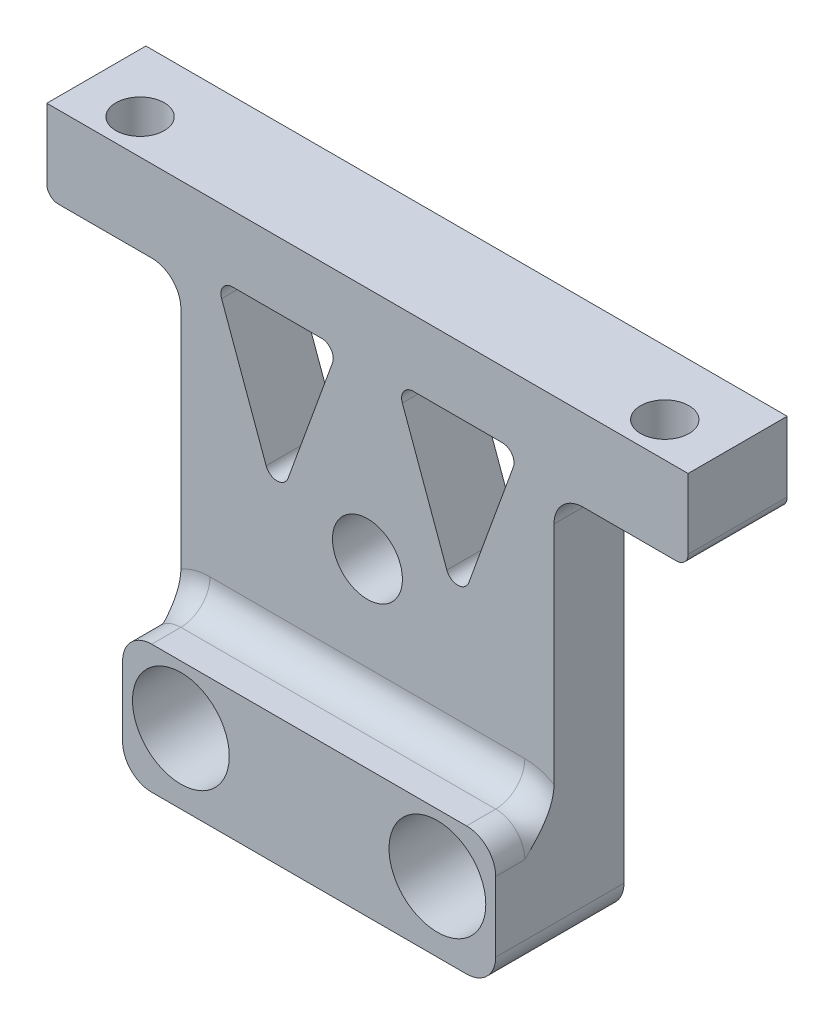
SolidWorks part; units mm, degrees
ref_plane "Front Plane" through (0, 0, 0) normal (0, 0, 1) x (1, 0, 0)
ref_plane "Top Plane" through (0, 0, 0) normal (0, 1, 0) x (1, 0, 0)
ref_plane "Right Plane" through (0, 0, 0) normal (1, 0, 0) x (0, 0, -1)
sketch "Esboço1" plane through (0, 0, 0) normal (0, 0, 1) x (1, 0, 0)
  line L0 (-194.983, 169.5286) -> (-202.6205, 148.5298)
  line L1 (-193, 100.2122) -> (-247, 100.2122)
  line L2 (-188, 105.2122) -> (-188, 164.5682)
  line L4 (-252, 105.2122) -> (-252, 164.5682)
  line L5 (-212.1375, 172.2122) -> (-196.8625, 172.2122)
  line L6 (-220, 183.5682) -> (-220, 100.2122) construction
  line L7 (-275, 183.5682) -> (-165, 183.5682)
  line L8 (-275, 183.5682) -> (-275, 171.5682)
  line L9 (-273, 169.5682) -> (-257, 169.5682)
  line L10 (-165, 183.5682) -> (-165, 171.5682)
  line L11 (-183, 169.5682) -> (-167, 169.5682)
  line L12 (-206.3795, 148.5298) -> (-214.017, 169.5286)
  line L13 (0, 100.2122) -> (-440, 100.2122) construction
  line L15 (-233.6205, 148.5298) -> (-225.983, 169.5286)
  line L16 (-227.8625, 172.2122) -> (-243.1375, 172.2122)
  line L17 (-245.017, 169.5286) -> (-237.3795, 148.5298)
  line L19 (-219, 172.2122) -> (-252, 172.2122) construction
  line L20 (-219, 172.2122) -> (-188, 172.2122) construction
  arc A0 (-202.6205, 148.5298) -> (-206.3795, 148.5298) centre (-204.5, 149.2135) cw
  arc A1 (-194.983, 169.5286) -> (-196.8625, 172.2122) centre (-196.8625, 170.2122) ccw
  arc A2 (-212.1375, 172.2122) -> (-214.017, 169.5286) centre (-212.1375, 170.2122) ccw
  circle A3 centre (-242, 112.2122) radius 8.3
  arc A4 (-225.983, 169.5286) -> (-227.8625, 172.2122) centre (-227.8625, 170.2122) ccw
  arc A5 (-243.1375, 172.2122) -> (-245.017, 169.5286) centre (-243.1375, 170.2122) ccw
  circle A6 centre (-198, 112.2122) radius 8.3
  arc A7 (-233.6205, 148.5298) -> (-237.3795, 148.5298) centre (-235.5, 149.2135) cw
  arc A8 (-167, 169.5682) -> (-165, 171.5682) centre (-167, 171.5682) ccw
  circle A9 centre (-220, 143.3622) radius 6
  arc A10 (-193, 100.2122) -> (-188, 105.2122) centre (-193, 105.2122) ccw
  arc A11 (-247, 100.2122) -> (-252, 105.2122) centre (-247, 105.2122) cw
  arc A12 (-188, 164.5682) -> (-183, 169.5682) centre (-183, 164.5682) cw
  arc A13 (-257, 169.5682) -> (-252, 164.5682) centre (-257, 164.5682) cw
  arc A14 (-275, 171.5682) -> (-273, 169.5682) centre (-273, 171.5682) ccw
  point P17 (-188, 100.2122)
  point P40 (-165, 169.5682)
  point P41 (-204.5, 143.3622)
  point P44 (-194.0069, 172.2122)
  point P47 (-214.9931, 172.2122)
  point P50 (-225.0069, 172.2122)
  point P53 (-245.9931, 172.2122)
  point P56 (-235.5, 143.3622)
  point P59 (-275, 169.5682)
  dimension "D6" = 5
  dimension "D9" = 5
  dimension "D10" = 2
  dimension "D11" = 2
  dimension "D4" = 10
  dimension "D5" = 10
  dimension "D7" = 110
  dimension "D8" = 14
  dimension "D1" = 43.15
  dimension "D2" = 12
  dimension "D3" = 12
extrude "Ressalto-extrusão1" add sketch "Esboço1" along normal blind 12
sketch "Esboço2" plane through (0, 0, 12) normal (0, 0, 1) x (1, 0, 0)
  line L6 (-252, 164.5682) -> (-252, 105.2122) construction
  line L7 (-247, 122.2122) -> (-193, 122.2122)
  line L8 (-252, 117.2122) -> (-252, 105.2122)
  line L9 (-247, 100.2122) -> (-193, 100.2122)
  line L10 (-188, 117.2122) -> (-188, 105.2122)
  line L11 (0, 100.2122) -> (-440, 100.2122) construction
  arc A0 (-193, 100.2122) -> (-188, 105.2122) centre (-193, 105.2122) ccw
  arc A1 (-193, 122.2122) -> (-188, 117.2122) centre (-193, 117.2122) cw
  arc A2 (-252, 105.2122) -> (-247, 100.2122) centre (-247, 105.2122) ccw
  arc A3 (-247, 122.2122) -> (-252, 117.2122) centre (-247, 117.2122) ccw
  circle A6 centre (-242, 112.2122) radius 8.3
  circle A7 centre (-242, 112.2122) radius 8.3
  circle A9 centre (-198, 112.2122) radius 8.3
  circle A10 centre (-198, 112.2122) radius 8.3
  point P10 (-188, 100.2122)
  point P13 (-188, 122.2122)
  point P18 (-252, 122.2122)
  dimension "D2" = 5
  dimension "D1" = 22
  dimension "D3" = 0
  dimension "D4" = 0
extrude "Ressalto-extrusão2" add sketch "Esboço2" along normal blind 10
fillet "Filete1" radius 5 3 edges at (-189.4645, 120.7477, 12) (-250.5355, 120.7477, 12) (-220, 122.2122, 12)
sketch "Esboço3" plane through (0, 169.5682, 0) normal (0, -1, 0) x (1, 0, 0)
  line L0 (-265, 12) -> (-265, 0) construction
  line L5 (-175, 12) -> (-175, 0) construction
  line L6 (-183, 12) -> (-167, 12) construction
  line L7 (-273, 12) -> (-257, 12) construction
  line L9 (-183, 0) -> (-167, 0) construction
  line L19 (-273, 0) -> (-257, 0) construction
  line L25 (-269.15, 6) -> (-260.85, 6) construction
  line L30 (-179.15, 6) -> (-170.85, 6) construction
  circle A0 centre (-265, 6) radius 4.15
  circle A1 centre (-175, 6) radius 4.15
  point P22 (-175, 6)
  point P31 (-265, 6)
  dimension "D4" = 8.3
  dimension "D1" = 8.3
extrude "Corte-extrusão1" cut sketch "Esboço3" against normal blind 15
sketch "Esboço5" plane through (0, 0, 0) normal (0, 0, -1) x (-1, 0, 0)
  line L8 (183.8551, 169.8918) -> (199.7305, 175.8987)
  line L9 (240.2695, 175.8987) -> (256.1449, 169.8918)
  line L10 (218.2305, 170.2377) -> (203.2695, 175.8987)
  line L11 (221.7695, 170.2377) -> (236.7305, 175.8987)
  line L16 (167, 169.5682) -> (183, 169.5682)
  line L17 (188, 164.5682) -> (188, 105.2122)
  line L18 (193, 100.2122) -> (247, 100.2122)
  line L19 (252, 105.2122) -> (252, 164.5682)
  line L20 (257, 169.5682) -> (273, 169.5682)
  line L21 (275, 171.5682) -> (275, 183.5682)
  line L22 (275, 183.5682) -> (165, 183.5682)
  line L23 (165, 183.5682) -> (165, 171.5682)
  line L24 (167, 169.5682) -> (182.0857, 169.5682)
  line L28 (257.9143, 169.5682) -> (273, 169.5682)
  line L29 (275, 171.5682) -> (275, 183.5682)
  line L30 (275, 183.5682) -> (165, 183.5682)
  line L31 (165, 183.5682) -> (165, 171.5682)
  arc A6 (256.1449, 169.8918) -> (257.9143, 169.5682) centre (257.9143, 174.5682) ccw
  arc A7 (236.7305, 175.8987) -> (240.2695, 175.8987) centre (238.5, 171.2222) cw
  arc A8 (218.2305, 170.2377) -> (221.7695, 170.2377) centre (220, 174.9141) ccw
  arc A9 (203.2695, 175.8987) -> (199.7305, 175.8987) centre (201.5, 171.2222) ccw
  arc A10 (182.0857, 169.5682) -> (183.8551, 169.8918) centre (182.0857, 174.5682) ccw
  arc A12 (165, 171.5682) -> (167, 169.5682) centre (167, 171.5682) ccw
  arc A13 (188, 164.5682) -> (183, 169.5682) centre (183, 164.5682) ccw
  arc A14 (188, 105.2122) -> (193, 100.2122) centre (193, 105.2122) ccw
  arc A15 (247, 100.2122) -> (252, 105.2122) centre (247, 105.2122) ccw
  arc A16 (257, 169.5682) -> (252, 164.5682) centre (257, 164.5682) ccw
  arc A17 (273, 169.5682) -> (275, 171.5682) centre (273, 171.5682) ccw
  arc A18 (165, 171.5682) -> (167, 169.5682) centre (167, 171.5682) ccw
  arc A23 (273, 169.5682) -> (275, 171.5682) centre (273, 171.5682) ccw
  dimension "D2" = 5
  dimension "D1" = 0
extrude "Ressalto-extrusão3" add sketch "Esboço5" along normal blind 5
sketch "Esboço6" plane through (0, 0, 0) normal (0, 0, -1) x (-1, 0, 0)
  line L0 (205.72, 125.0703) -> (203.72, 125.0703) construction
  line L1 (205.72, 121.2467) -> (203.72, 121.2467)
  line L4 (205.72, 121.2467) -> (205.72, 128.8939)
  line L5 (205.72, 128.8939) -> (203.72, 128.8939)
  line L8 (204.72, 122.5355) -> (204.72, 127.6051) construction
  line L9 (203.72, 121.2467) -> (203.72, 128.8939)
  point P12 (204.72, 125.0703)
  point P13 (204.72, 125.0703)
  dimension "D1" = 2
extrude "Ressalto-extrusão4" add sketch "Esboço6" along normal blind 9
